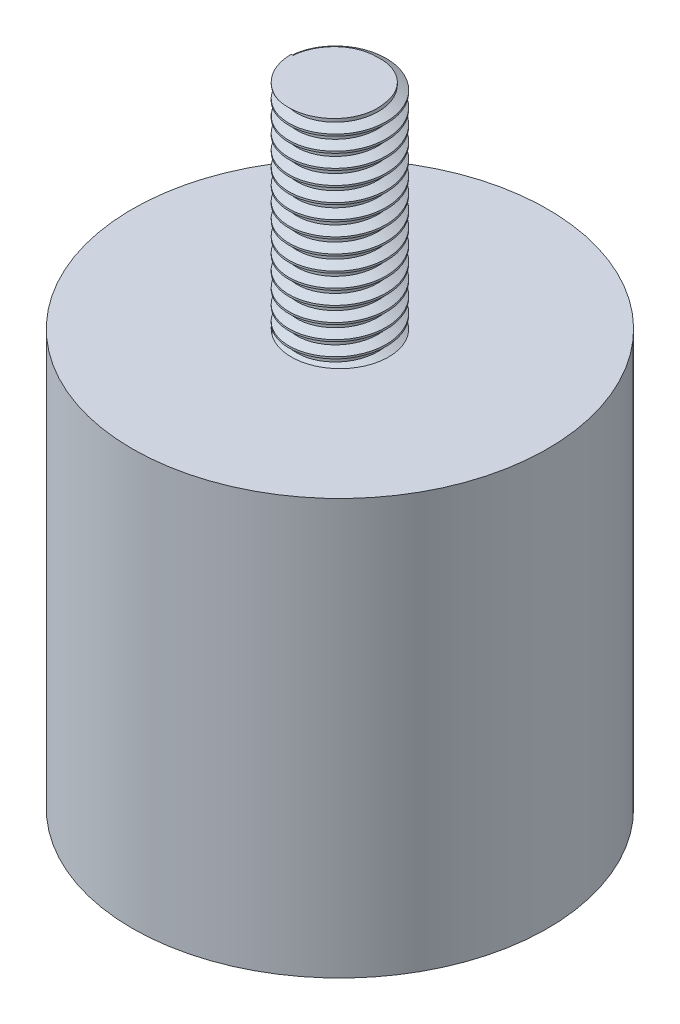
SolidWorks part; units mm, degrees
ref_plane "Ön Düzlem" through (0, 0, 0) normal (0, 0, 1) x (1, 0, 0)
ref_plane "Üst Düzlem" through (0, 0, 0) normal (0, 1, 0) x (1, 0, 0)
ref_plane "Sağ Düzlem" through (0, 0, 0) normal (1, 0, 0) x (0, 0, -1)
sketch "Çizim2" plane through (0, 0, 0) normal (0, 0, 1) x (1, 0, 0)
  line L1 (0, 17.5) -> (-17.5, 17.5)
  line L2 (0, 17.5) -> (0, -17.5)
  line L3 (0, -17.5) -> (-17.5, -17.5)
  line L4 (-17.5, 17.5) -> (-17.5, -17.5)
  line L5 (0, 17.5) -> (-4.1, 17.5)
  line L6 (0, 17.5) -> (0, 35.5)
  line L7 (0, 35.5) -> (-4.1, 35.5)
  line L8 (-4.1, 17.5) -> (-4.1, 35.5)
  point P4 (0, 0)
  dimension "D1" = 17.5
  dimension "17" = 35
  dimension "D3" = 4.1
  dimension "D4" = 18
revolve "Döndür1" add sketch "Çizim2" angle 360 about L2 region at (-8.75, 0, 0) region at (-2.05, 26.5, 0)
thread "Diş1" pitch 1.25 method cut profile "Diş Profili1" start angle 0, offset 1, length 0, pitch 1.25, diameter 8.2
ref_plane "Düzlem1" through (-4.1, 36.5, 0) normal (0, 0, 1) x (-1, 0, 0)
sketch "Diş Profili1" plane through (-4.1, 36.5, 0) normal (0, 0, 1) x (-1, 0, 0)
  line L0 (0, 0) -> (0, 1.25) construction
  line L11 (0, 0) -> (0, 1.0937)
  line L12 (0, 1.0937) -> (-0.6766, 0.7031)
  line L13 (-0.6766, 0.7031) -> (-0.6766, 0.3906)
  line L15 (-0.6766, 0.3906) -> (0, 0)
  line L17 (-0.6766, 0.5469) -> (0, 0.5469) construction
  point P2 (0, 0)
  dimension "Pitch" = 1.25
  dimension "Profile_Angle" = 60
  dimension "Profile_Land" = 0.3125
  dimension "Profile_Height" = 0.6766
hole_wizard "M8 Dişli Delik1" positions "Çizim5" profile "Çizim6" tap size "M8" standard "ISO"
sketch "Çizim5" plane through (0, -17.5, 0) normal (0, -1, 0) x (-1, 0, 0)
  point P0 (0, 0)
sketch "Çizim6" plane through (0, -17.5, 0) normal (1, 0, 0) x (0, 0, -1)
  line L0 (0, 0) -> (0, 17.0429)
  line L1 (0, 17.0429) -> (3.4, 15)
  line L2 (3.4, 15) -> (3.4, 0.625)
  line L3 (3.4, 0.625) -> (4.025, 0)
  line L5 (4.025, 0) -> (0, 0)
  line L6 (-3.4, 0.625) -> (-4.025, 0) construction
  line L10 (0, 17.0429) -> (-3.4, 15) construction
  line L11 (0, -6.35) -> (0, 107.95) construction
  dimension "Tap Drill Dia." = 6.8
  dimension "Tap Drill Depth" = 15
  dimension "Near C'Sink Dia." = 8.05
  dimension "Near C'Sink Angle" = 90
  dimension "Drill Angle" = 118
cosmetic thread "Delik Dişi1" parameters "D1"=12, "D2"=8
